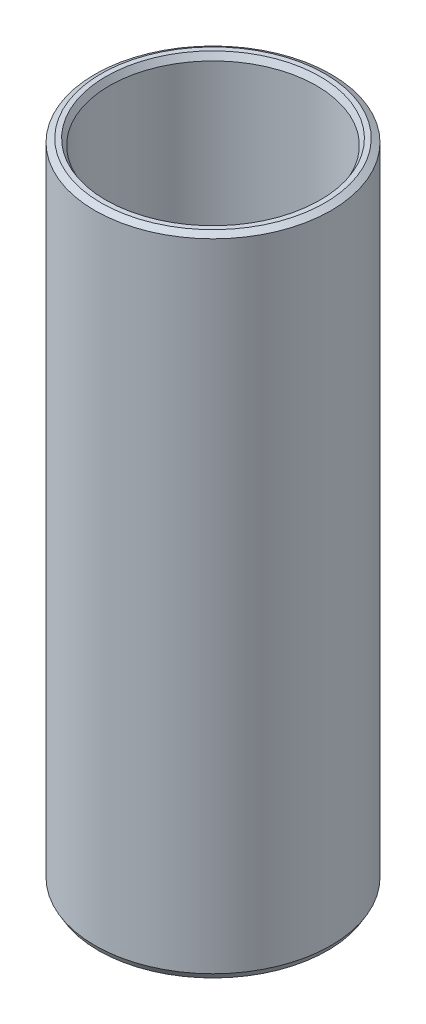
SolidWorks part; units mm, degrees
ref_plane "Front Plane" through (0, 0, 0) normal (0, 0, 1) x (1, 0, 0)
ref_plane "Top Plane" through (0, 0, 0) normal (0, 1, 0) x (1, 0, 0)
ref_plane "Right Plane" through (0, 0, 0) normal (1, 0, 0) x (0, 0, -1)
sketch "Sketch1" plane through (0, 0, 0) normal (0, 1, 0) x (1, 0, 0)
  circle A0 centre (0, 0) radius 47.5
  dimension "SLEEVE_OD" = 95
extrude "Boss-Extrude1" add sketch "Sketch1" along normal blind 259.9434
sketch "Sketch2" plane through (0, 0, 0) normal (0, 1, 0) x (1, 0, 0)
  circle A0 centre (0, 0) radius 41.6464
  dimension "BORE_D" = 83.2927
extrude "Cut-Extrude1" cut sketch "Sketch2" along normal through all
chamfer "Chamfer1" distance 1.4333 angle 60 4 edges at (0, 259.9434, 41.6464) (0, 0, 41.6464) (0, 0, 47.5) (0, 259.9434, 47.5) first distance on face at (0, 259.9434, 41.6464) first distance on face at (0, 0, 41.6464) first distance on face at (0, 259.9434, 47.5)
